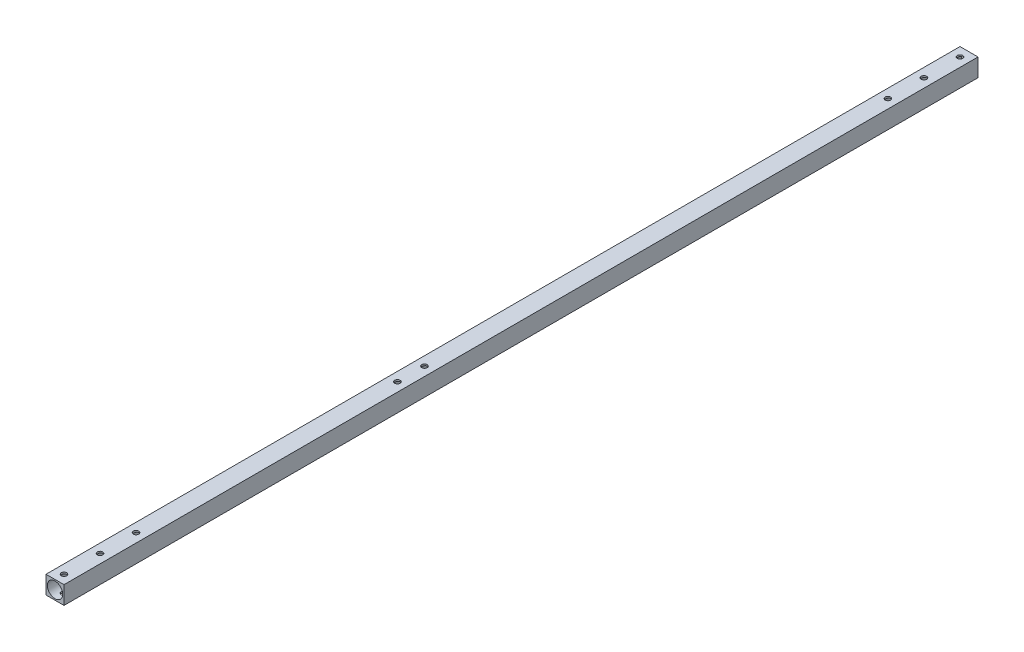
SolidWorks part; units mm, degrees
material "Thornel VCB-20 Carbon Cloth"
ref_plane "Front Plane" through (0, 0, 0) normal (0, 0, 1) x (1, 0, 0)
ref_plane "Top Plane" through (0, 0, 0) normal (0, 1, 0) x (1, 0, 0)
ref_plane "Right Plane" through (0, 0, 0) normal (1, 0, 0) x (0, 0, -1)
sketch "Sketch1" plane through (0, 0, 0) normal (0, 0, 1) x (1, 0, 0)
  line L1 (-5, -5) -> (5, -5)
  line L2 (-5, -5) -> (-5, 5)
  line L3 (-5, 5) -> (5, 5)
  line L4 (5, -5) -> (5, 5)
  line L5 (-5, -5) -> (5, 5) construction
  line L6 (-5, 5) -> (5, -5) construction
  circle A0 centre (0, 0) radius 4.25
  point P0 (0, 0)
  dimension "D3" = 8.5
  dimension "D1" = 10
  dimension "D2" = 10
extrude "Boss-Extrude1" add sketch "Sketch1" along normal blind 507.4
sketch "Sketch2" plane through (0, 5, 0) normal (0, 1, 0) x (1, 0, 0)
  line L0 (0, 0) -> (0, -5) construction
  line L1 (0, -5) -> (0, -25) construction
  line L2 (0, -25) -> (0, -45) construction
  line L3 (0, -507.4) -> (0, -502.4) construction
  line L4 (5, -507.4) -> (-5, -507.4) construction
  line L5 (0, -502.4) -> (0, -482.4) construction
  line L6 (0, -482.4) -> (0, -462.4) construction
  line L7 (0, -5) -> (0, -302.3) construction
  line L8 (0, -302.3) -> (0, -317.3) construction
  circle A0 centre (0, -5) radius 1.5
  circle A1 centre (0, -25) radius 1.5
  circle A2 centre (0, -45) radius 1.5
  circle A3 centre (0, -502.4) radius 1.5
  circle A4 centre (0, -482.4) radius 1.5
  circle A5 centre (0, -462.4) radius 1.5
  circle A6 centre (0, -302.3) radius 1.5
  circle A7 centre (0, -317.3) radius 1.5
  point P21 (0, -309.8)
  dimension "D3" = 3
  dimension "D4" = 5
  dimension "D6" = 3
  dimension "D8" = 15
  dimension "D1" = 5
  dimension "D2" = 20
  dimension "D5" = 20
  dimension "D7" = 304.8
extrude "Cut-Extrude1" cut sketch "Sketch2" against normal through all
